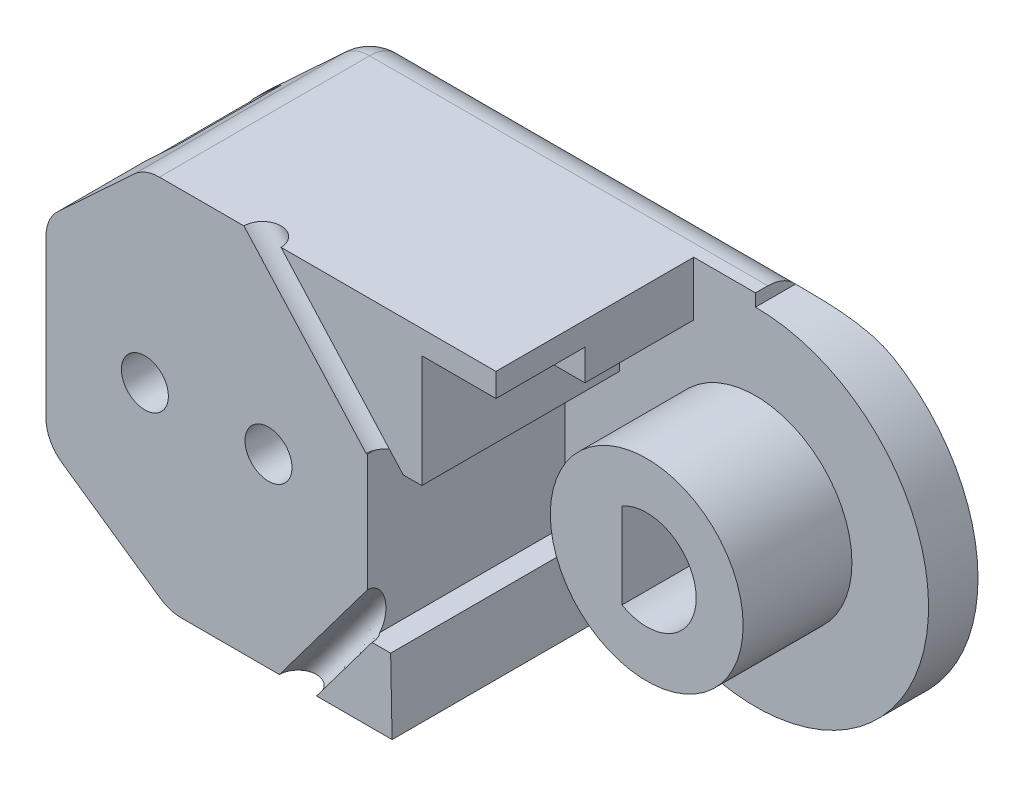
SolidWorks part; units mm, degrees
ref_plane "Front Plane" through (0, 0, 0) normal (0, 0, 1) x (1, 0, 0)
ref_plane "Top Plane" through (0, 0, 0) normal (0, 1, 0) x (1, 0, 0)
ref_plane "Right Plane" through (0, 0, 0) normal (1, 0, 0) x (0, 0, -1)
sketch "Sketch2" plane through (0, 0, 0) normal (0, 0, 1) x (1, 0, 0)
  line L1 (-2.5, 7.5) -> (-16.7, 7.5)
  line L2 (-20.7, 3.7934) -> (-20.7, -4.0316)
  line L3 (-15.7, -7.5) -> (-6.7, -7.5)
  line L4 (-6.7, -7.5) -> (-4.2, -5.6)
  line L5 (-2.5, 7.5) -> (0, 7.5)
  line L7 (0, 7) -> (0, 7.5)
  line L8 (-20.7, 3.7934) -> (-16.7, 7.5)
  line L9 (-20.7, -4.0316) -> (-15.7, -7.5)
  arc A1 (-4.2, -5.6) -> (7, 0) centre (0, 0) ccw
  arc A2 (7, 0) -> (0, 7) centre (0, 0) ccw
  dimension "D1" = 7
  dimension "D2" = 4
  dimension "D3" = 5
  dimension "D4" = 7.5
  dimension "D5" = 15
  dimension "D7" = 2.5
  dimension "D8" = 14
extrude "Boss-Extrude1" add sketch "Sketch2" along normal blind 2 contours A1 A2 L7 L5 L1 L8 L2 L9 L3 L4
sketch "Sketch4" plane through (0, 0, 2) normal (0, 0, 1) x (1, 0, 0)
  line L7 (-15.7, -7.5) -> (-6.7, -7.5)
  line L8 (-6.7, -7.5) -> (-6.7591, -4.5)
  line L9 (-6.7591, -4.5) -> (-7.7, -4.5)
  line L10 (-16.7, 7.5) -> (-2.5, 7.5)
  line L13 (-5.5, 2) -> (-5.5, 5.3)
  line L14 (-5.5, 5.3) -> (-2.5, 5.3)
  line L21 (-20.7, -4.0316) -> (-15.7, -7.5)
  line L24 (-16.7, 7.5) -> (-20.7, 3.7934)
  line L25 (-20.7, -4.0316) -> (-20.7, 3.7934)
  line L26 (-7.7, 2) -> (-5.5, 2)
  line L29 (-7.7, 2) -> (-7.7, -4.5)
  line L30 (-2.5, 7.5) -> (-2.5, 5.3)
  point P2 (-5.5, 3.65)
  dimension "D1" = 13
  dimension "D2" = 2.5
  dimension "D3" = 3
  dimension "D4" = 3
extrude "Boss-Extrude2" add sketch "Sketch4" along normal blind 8
ref_point "Point1"
sketch "Sketch22" plane through (0, 0, 2) normal (0, 0, 1) x (1, 0, 0)
  line L0 (0, 5.3) -> (-14, 5.3) construction
  line L1 (0, 4) -> (-14, 4) construction
  line L2 (-14, 4) -> (-14, 5.3) construction
  circle A0 centre (0, 0) radius 5.3 construction
  circle A1 centre (0, 0) radius 4 construction
  dimension "D1" = 14
  dimension "D2" = 10.6
  dimension "D3" = 8
sketch "Sketch24" plane through (0, 0, 2) normal (0, 0, 1) x (1, 0, 0)
  circle A0 centre (0, 0) radius 3.9
  dimension "D1" = 7.8
extrude "Boss-Extrude5" add sketch "Sketch24" along normal blind 4.4
sketch "Sketch29" plane through (-5.5, 0, 0) normal (1, 0, 0) x (0, 0, -1)
  line L0 (-1.9279, 3.9758) -> (-10, 3.9758) construction
  line L1 (-10, 2) -> (-10, 5.3) construction
sketch "Sketch30" plane through (-5.5, 0, 0) normal (1, 0, 0) x (0, 0, -1)
  line L0 (-6.4086, 3.9758) -> (-6.4086, 5.3)
  line L1 (-6.4086, 3.9758) -> (-2, 3.9758)
  line L2 (-6.4086, 5.3) -> (-2, 5.3)
  line L3 (-2, 3.9758) -> (-2, 5.3)
  line L6 (-2, 2) -> (-2, 5.3) construction
  line L7 (-10, 5.3) -> (-2, 5.3) construction
  point P0 (-4.4086, 5.3)
  point P6 (0, 0)
  point P8 (0, 0)
  point P9 (0, 0)
  dimension "D1" = 4.4086
extrude "Cut-Extrude12" cut sketch "Sketch30" against normal blind 16
ref_plane "Plane1" through (0, 0, 10) normal (0, 0, 1) x (1, 0, 0)
sketch "Sketch8" plane through (0, 0, 2) normal (0, 0, 1) x (1, 0, 0)
  circle A1 centre (0, 0) radius 3.8
  circle A2 centre (0, 0) radius 2.5
sketch "Sketch28" plane through (0, 0, 6.4) normal (0, 0, 1) x (1, 0, 0)
  line L0 (-1, 1.7321) -> (-1, -1.7321)
  arc A0 (-1, -1.7321) -> (-1, 1.7321) centre (0, 0) ccw
  dimension "D1" = 1
  dimension "D2" = 2
extrude "Cut-Extrude11" cut sketch "Sketch28" against normal through all
sketch "Sketch33" plane through (0, 0, 10) normal (0, 0, 1) x (1, 0, 0)
  line L0 (-7, 2) -> (-0.5657, -5.1566) construction
  line L2 (-8.2591, -4.5) -> (-2.6001, 3.0469) construction
  dimension "D1" = 1.5
  dimension "D2" = 1.5
fillet "Fillet1" radius 1.5 9 edges at (-11.2, -7.5, 0) (-8.35, 7.5, 0) (-18.7, 5.6467, 0) (-18.2, -5.7658, 0) (-20.7, -0.1191, 0) (-15.7, -7.5, 5) (-20.7, -4.0316, 5) (-20.7, 3.7934, 5) (-16.7, 7.5, 5)
sketch "Sketch34" plane through (0, 2, 0) normal (0, -1, 0) x (1, 0, 0)
  line L0 (-5.5, 1.9279) -> (-5.5, 10) construction
  line L1 (8.25, 10) -> (-8.25, 10) construction
  circle A0 centre (-7, 10) radius 0.75
  point P2 (0, 0)
  dimension "D1" = 1.5
  dimension "D2" = 1.5
extrude "Cut-Extrude13" cut sketch "Sketch34" along direction (0.6686, -0.7436, 0) on the side against the normal blind 8
sketch "Sketch35" plane through (0, -4.5, 0) normal (0, 1, 0) x (1, 0, 0)
  circle A0 centre (-8.2591, -10) radius 0.75
extrude "Cut-Extrude14" cut sketch "Sketch35" along direction (0.5999, 0.8001, 0) on the side against the normal blind 8 and the other way blind 3
sketch "Sketch36" plane through (0, 0, 10) normal (0, 0, 1) x (1, 0, 0)
  line L2 (-7.7, -2.7542) -> (-7.7, 2) construction
  circle A0 centre (-11.7, 0) radius 0.95
  circle A1 centre (-16.7, 0) radius 0.95
  dimension "D1" = 4
  dimension "D2" = 5
extrude "Cut-Extrude15" cut sketch "Sketch36" against normal blind 8
sketch "Sketch37" plane through (0, 0, 0) normal (0, 0, -1) x (-1, 0, 0)
  circle A0 centre (11.7, 0) radius 2
  circle A1 centre (16.7, 0) radius 2
extrude "Cut-Extrude16" cut sketch "Sketch37" against normal blind 4.5
sketch "Sketch38" plane through (0, 0, 10) normal (0, 0, 1) x (1, 0, 0)
  line L0 (-5.5, 5.3) -> (-2.5, 5.3)
  line L1 (-5.5, 5.3) -> (-5.5, 6.55)
  line L2 (-2.5, 5.3) -> (-2.5, 6.55)
  line L3 (-5.5, 6.55) -> (-2.5, 6.55)
  dimension "D1" = 1.25
extrude "Cut-Extrude17" cut sketch "Sketch38" against normal blind 3.6
ref_plane "Plane2" through (0, 0, 6.4) normal (0, 0, 1) x (1, 0, 0)
